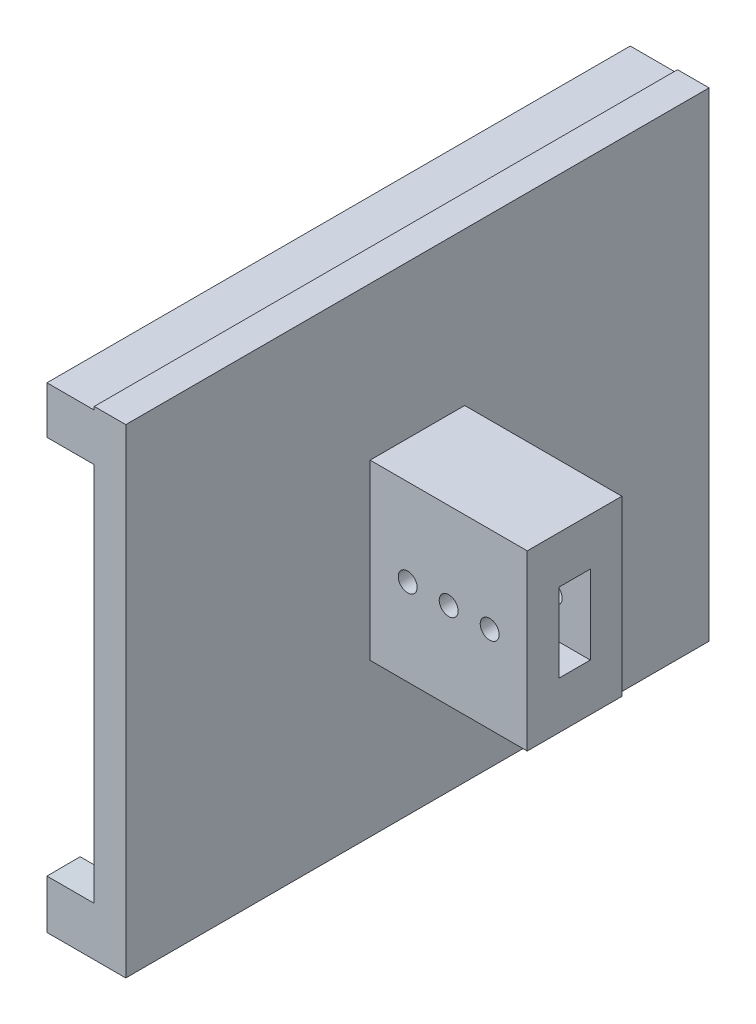
SolidWorks part; units mm, degrees
material "ABS PC"
ref_plane "Front Plane" through (0, 0, 0) normal (0, 0, 1) x (1, 0, 0)
ref_plane "Top Plane" through (0, 0, 0) normal (0, 1, 0) x (1, 0, 0)
ref_plane "Right Plane" through (0, 0, 0) normal (1, 0, 0) x (0, 0, -1)
sketch "Sketch1" plane through (0, 0, 0) normal (0, 0, 1) x (1, 0, 0)
  line L1 (-1.1918, 1.25) -> (3.7918, 1.25)
  line L2 (-1.1918, 1.25) -> (-1.1918, -1.25)
  line L3 (-1.1918, -1.25) -> (3.7918, -1.25)
  line L4 (3.7918, 1.25) -> (3.7918, -1.25)
  line L5 (-1.1918, 1.25) -> (3.7918, -1.25) construction
  line L6 (-1.1918, -1.25) -> (3.7918, 1.25) construction
  circle A0 centre (0, 0) radius 0.3
  circle A1 centre (1.3, 0) radius 0.3
  circle A2 centre (2.6, 0) radius 0.3
  dimension "D1" = 3
  dimension "D3" = 0.6
  dimension "D4" = 1.3
  dimension "D2" = 2.5
ref_plane "Plane1" through (0, 0, 1) normal (0, 0, 1) x (1, 0, 0)
sketch "Sketch2" plane through (0, 0, 1) normal (0, 0, 1) x (1, 0, 0)
  line L4 (3.7918, 1.25) -> (-1.1918, 1.25)
  line L5 (3.7918, -1.25) -> (3.7918, 1.25)
  line L6 (-1.1918, -1.25) -> (3.7918, -1.25)
  line L7 (-1.1918, 1.25) -> (-1.1918, -1.25)
  line L8 (3.7918, 1.25) -> (-1.1918, 1.25)
  line L9 (3.7918, -1.25) -> (3.7918, 1.25)
  line L10 (-1.1918, -1.25) -> (3.7918, -1.25)
  line L11 (-1.1918, 1.25) -> (-1.1918, -1.25)
  circle A1 centre (2.6, 0) radius 0.3
  circle A2 centre (2.6, 0) radius 0.3
  circle A3 centre (1.3, 0) radius 0.3
  circle A4 centre (1.3, 0) radius 0.3
  circle A5 centre (0, 0) radius 0.3
  circle A6 centre (0, 0) radius 0.3
  dimension "D1" = 0
  dimension "D2" = 0
  dimension "D3" = 0
  dimension "D4" = 0
extrude "Boss-Extrude1" add sketch "Sketch1" against normal blind 1
sketch "Sketch4" plane through (-1.1918, 0, 0) normal (-1, 0, 0) x (0, 0, 1)
  line L0 (0, 7.6) -> (0, -7.6)
  line L1 (0, 7.6) -> (-8.75, 7.6)
  line L2 (0, -7.6) -> (-8.75, -7.6)
  line L3 (-8.75, 7.6) -> (-8.75, -7.6)
  line L4 (0, 1.25) -> (0, -1.25) construction
  line L5 (-7.2, -6) -> (-7.2, 6) construction
  line L6 (-7.2, 0) -> (0, 0) construction
  circle A0 centre (-7.2, -6) radius 0.5
  circle A1 centre (-7.2, 6) radius 0.5
  point P8 (0, 0)
  line M7 (0, -1.25) -> (0, 1.25)
  line M8 (0, 1.25) -> (-1, 1.25)
  line M9 (-1, 1.25) -> (-1, -1.25)
  line M10 (-1, -1.25) -> (0, -1.25)
  dimension "D4" = 1
  dimension "D1" = 8.75
  dimension "D2" = 15.2
  dimension "D3" = 12
  dimension "D5" = 1.55
extrude "Boss-Extrude2" add sketch "Sketch4" along normal blind 1 contours A0 | A1 | L1 L3 L2 L0 A1 A0 M10 M9 M8 | M10 M7 M8 M9 region at (-1.1918, 0, -4.4157) region at (-1.1918, 0, -0.5) region at (-1.1918, -6, -7.2) region at (-1.1918, 6, -7.2)
extrude "Boss-Extrude3" add sketch "Sketch4<3>" along normal blind 1.5 contours A0 | A1
sketch "Sketch4<3>" plane through (-1.1918, 0, 0) normal (-1, 0, 0) x (0, 0, 1) same geometry as "Sketch4"
ref_plane "Plane2" through (0, 0, 0.5) normal (0, 0, 1) x (1, 0, 0)
mirror "Mirror3" about plane through (0, 0, 0.5) normal (0, 0, 1) of bodies 103
sketch "Sketch5" plane through (0, 0, 0.5) normal (0, 0, 1) x (1, 0, 0)
  line L0 (-1.1918, -2.75) -> (3.7918, -2.75)
  line L1 (3.7918, -2.75) -> (3.7918, -1.25)
  line L2 (3.7918, 1.25) -> (3.7918, 2.75)
  line L3 (3.7918, 2.75) -> (-1.1918, 2.75)
  line L4 (-1.1918, 1.25) -> (-1.1918, -1.25)
  line L8 (3.7918, -1.25) -> (3.7918, 1.25)
  line L9 (3.7918, 1.25) -> (-1.1918, 1.25)
  line L10 (-1.1918, 1.25) -> (-1.1918, 7.6)
  line L11 (-1.1918, 7.6) -> (-2.1918, 7.6)
  line L12 (-2.1918, 7.6) -> (-2.1918, -7.6)
  line L13 (-2.1918, -7.6) -> (-1.1918, -7.6)
  line L14 (-1.1918, -7.6) -> (-1.1918, -1.25)
  line L15 (-1.1918, -1.25) -> (3.7918, -1.25)
  line L16 (3.7918, -1.25) -> (3.7918, 1.25)
  line L17 (3.7918, 1.25) -> (-1.1918, 1.25)
  line L18 (-1.1918, 1.25) -> (-1.1918, 7.6)
  line L19 (-1.1918, 7.6) -> (-2.1918, 7.6)
  line L20 (-2.1918, 7.6) -> (-2.1918, -7.6)
  line L21 (-2.1918, -7.6) -> (-1.1918, -7.6)
  line L22 (-1.1918, -7.6) -> (-1.1918, -1.25)
  line L23 (-1.1918, -1.25) -> (3.7918, -1.25)
  dimension "D2" = 1.5
  dimension "D3" = 1.5
  dimension "D1" = 0
extrude "Boss-Extrude4" add sketch "Sketch5" along normal blind 1 and the other way blind 1 contours L21 L22 L4 L18 L19 L20 region at (-1.6918, 0, 0.5)
extrude "Boss-Extrude5" add sketch "Sketch5<4>" along normal blind 1.5 and the other way blind 1.5 contours L23 L22 L0 L1 | L18 L17 L2 L3 region at (1.3, -2, 0.5) region at (1.3, 2, 0.5)
sketch "Sketch5<4>" plane through (0, 0, 0.5) normal (0, 0, 1) x (1, 0, 0) same geometry as "Sketch5"
sketch "Sketch7" plane through (-2.1918, 0, 0) normal (-1, 0, 0) x (0, 0, 1)
  line L0 (-7.2, -7.5) -> (-7.2, -4.5)
  line L2 (-7.2, -7.5) -> (-8.75, -7.5)
  line L3 (-8.75, 7.6) -> (-8.75, -7.6) construction
  line L4 (-8.75, -7.5) -> (-8.75, -4.5)
  line L5 (-8.75, -4.5) -> (0.5, -4.5)
  line L6 (9.75, 7.6) -> (9.75, -7.6) construction
  line L7 (9.75, -4.5) -> (9.75, -7.6)
  line L8 (9.75, -7.6) -> (-7.2, -7.5)
  line L9 (-7.2, 4.5) -> (-7.2, 7.5)
  line L10 (0.5, 4.5) -> (-8.75, 4.5)
  line L11 (9.75, 4.5) -> (9.75, 7.5)
  line L12 (9.75, 7.5) -> (-8.75, 7.5)
  line L13 (-8.75, 7.5) -> (-8.75, 4.5)
  line L14 (0.5, 4.5) -> (0.5, 6)
  line L15 (0.5, 6) -> (9.75, 6)
  line L16 (0.5, -4.5) -> (0.5, -6)
  line L17 (0.5, -6) -> (9.75, -6.05)
  circle A0 centre (-7.2, 6) radius 0.5 construction
  circle A1 centre (-7.2, -6) radius 0.5 construction
  point P4 (-7.2, -6)
  point P18 (-7.2, 6)
  point P28 (8.2, 6)
  line M3 (-8.75, 7.6) -> (-8.75, -7.6)
  line M5 (9.75, -7.6) -> (9.75, 7.6)
  circle M7 centre (-7.2, 6) radius 0.5
  circle M8 centre (-7.2, -6) radius 0.5
  circle M9 centre (8.2, 6) radius 0.5
  circle M10 centre (8.2, -6) radius 0.5
  dimension "D1" = 3
  dimension "D2" = 3
extrude "Boss-Extrude6" add sketch "Sketch7" along normal blind 1.5 contours L12 L9 M5 M7 M9 | L8 L5 L0 M5 M8 M10 | L5 L2 L0 M3 M8 | L9 L12 M3 M7 region at (-2.1918, -6, -8.0269) region at (-2.1918, -6.3153, -0.1215) region at (-2.1918, 6, -8.0269) region at (-2.1918, 6.2852, -0.1866)
